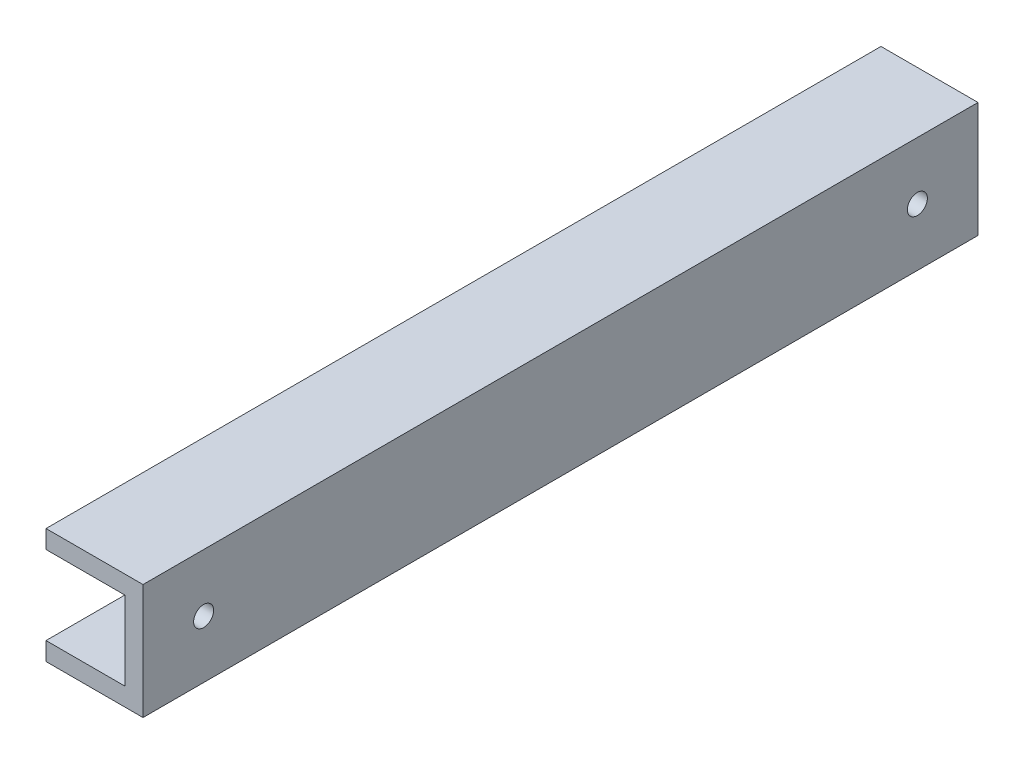
SolidWorks part; units mm, degrees
ref_plane "前视基准面" through (0, 0, 0) normal (0, 0, 1) x (1, 0, 0)
ref_plane "上视基准面" through (0, 0, 0) normal (0, 1, 0) x (1, 0, 0)
ref_plane "右视基准面" through (0, 0, 0) normal (1, 0, 0) x (0, 0, -1)
sketch "草图1" plane through (0, 0, 0) normal (0, 0, 1) x (1, 0, 0)
  line L1 (0, 0) -> (13, 0)
  line L2 (0, 0) -> (0, 13)
  line L3 (0, 13) -> (13, 13)
  line L4 (13, 0) -> (13, 13)
  dimension "D1" = 13
  dimension "D2" = 13
extrude "拉伸-薄壁1" add sketch "草图1" along normal blind 137.7 thin thin type one direction wall 3
sketch "草图2" plane through (-3, 0, 0) normal (-1, 0, 0) x (0, 0, 1)
  line L0 (0, 16) -> (0, -3) construction
  line L1 (137.7, 16) -> (137.7, -3) construction
  circle A0 centre (10, 6.5) radius 1.65
  circle A1 centre (127.7, 6.5) radius 1.65
  dimension "D1" = 3.3
  dimension "D2" = 3.3
  dimension "D3" = 10
  dimension "D4" = 10
extrude "切除-拉伸1" cut sketch "草图2" against normal blind 30
sketch "草图3" plane through (-3, 0, 0) normal (-1, 0, 0) x (0, 0, 1)
  line L1 (-5.2954, 23.3125) -> (179.0376, 23.3125)
  line L2 (-5.2954, 23.3125) -> (-5.2954, -16.5507)
  line L3 (-5.2954, -16.5507) -> (179.0376, -16.5507)
  line L4 (179.0376, 23.3125) -> (179.0376, -16.5507)
extrude "切除-拉伸2" cut sketch "草图3" against normal blind 3
sketch "草图4" plane through (13, 0, 0) normal (-1, 0, 0) x (0, 0, 1)
  line L0 (137.7, 13) -> (0, 13) construction
  line L1 (23, 13) -> (28, 13)
  line L2 (23, 13) -> (23, 0)
  line L3 (23, 0) -> (28, 0)
  line L4 (28, 13) -> (28, 0)
  line L5 (137.7, 0) -> (0, 0) construction
  line L6 (137.7, 13) -> (0, 13) construction
  line L7 (109.7, 13) -> (114.7, 13)
  line L8 (109.7, 13) -> (109.7, 0)
  line L9 (109.7, 0) -> (114.7, 0)
  line L10 (114.7, 13) -> (114.7, 0)
  line L11 (137.7, 0) -> (0, 0) construction
  line L12 (137.7, 0) -> (137.7, 13) construction
  line L13 (0, 0) -> (0, 13) construction
  dimension "D1" = 23
  dimension "D2" = 23
  dimension "D3" = 5
  dimension "D4" = 5
extrude "凸台-拉伸1" add sketch "草图4" along normal blind 10
sketch "草图5" plane through (13, 0, 0) normal (-1, 0, 0) x (0, 0, 1)
  line L0 (28, 0) -> (28, 13) construction
  line L1 (28, 9) -> (109.7, 9)
  line L2 (28, 9) -> (28, 4)
  line L3 (28, 4) -> (109.7, 4)
  line L4 (109.7, 9) -> (109.7, 4)
  line L5 (109.7, 13) -> (109.7, 0) construction
  line L6 (109.7, 0) -> (28, 0) construction
  dimension "D1" = 5
  dimension "D2" = 4
extrude "凸台-拉伸2" add sketch "草图5" along normal blind 10
sketch "草图6" plane through (13, 0, 0) normal (-1, 0, 0) x (0, 0, 1)
  line L1 (23, 13) -> (114.7, 13)
  line L2 (23, 13) -> (23, 0)
  line L3 (23, 0) -> (114.7, 0)
  line L4 (114.7, 13) -> (114.7, 0)
extrude "凸台-拉伸3" add sketch "草图6" along normal blind 10
sketch "草图7" plane through (3, 0, 0) normal (-1, 0, 0) x (0, 0, 1)
  line L0 (23, 13) -> (23, 0) construction
  line L1 (23, 9) -> (114.7, 9)
  line L2 (23, 9) -> (23, 4)
  line L3 (23, 4) -> (114.7, 4)
  line L4 (114.7, 9) -> (114.7, 4)
  line L5 (114.7, 0) -> (114.7, 13) construction
  line L6 (137.7, 13) -> (0, 13) construction
  dimension "D1" = 5
  dimension "D2" = 4
extrude "凸台-拉伸4" [suppressed] add sketch "草图7" along normal blind 3
sketch "草图8" plane through (3, 0, 0) normal (-1, 0, 0) x (0, 0, 1)
  line L0 (23, 13) -> (23, 0) construction
  line L1 (23, 9) -> (114.7, 9)
  line L2 (23, 9) -> (23, 4)
  line L3 (23, 4) -> (114.7, 4)
  line L4 (114.7, 9) -> (114.7, 4)
  line L5 (114.7, 0) -> (114.7, 13) construction
  line L6 (137.7, 13) -> (0, 13) construction
  dimension "D1" = 5
  dimension "D2" = 4
extrude "切除-拉伸3" cut sketch "草图8" against normal blind 3
chamfer "倒角1" distance 3 angle 45 2 edges at (6, 6.5, 114.7) (6, 6.5, 23)
chamfer "倒角2" distance 4 angle 45 2 edges at (13, 6.5, 114.7) (13, 6.5, 23)
